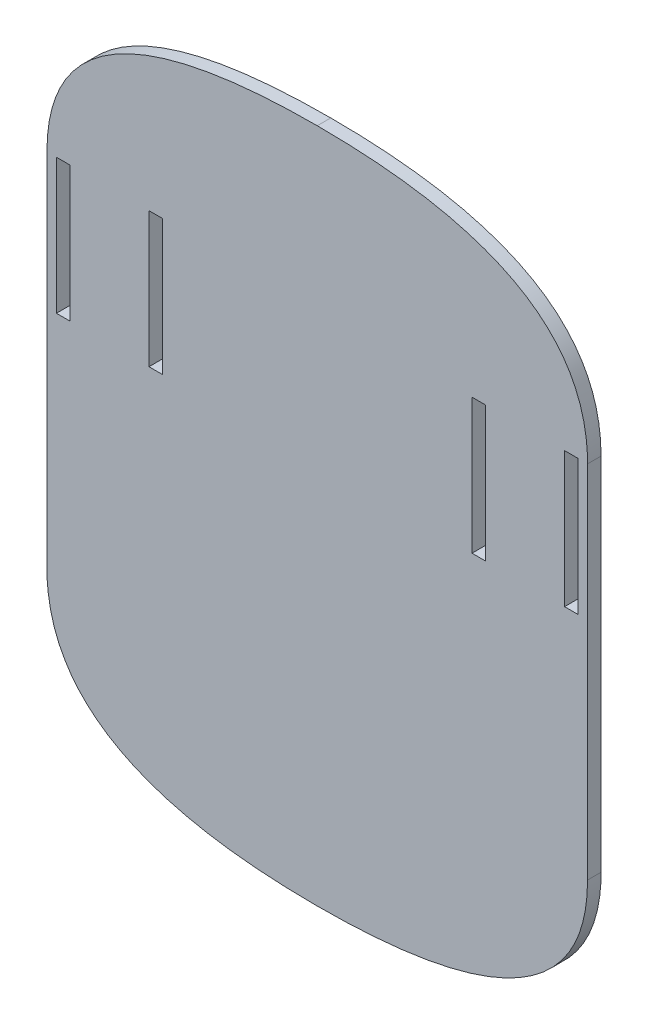
SolidWorks part; units mm, degrees
ref_plane "Front Plane" through (0, 0, 0) normal (0, 0, 1) x (1, 0, 0)
ref_plane "Top Plane" through (0, 0, 0) normal (0, 1, 0) x (1, 0, 0)
ref_plane "Right Plane" through (0, 0, 0) normal (1, 0, 0) x (0, 0, -1)
sketch "Sketch1" plane through (0, 0, 0) normal (0, 0, 1) x (1, 0, 0)
  line L1 (0, 0) -> (203.2, 0)
  line L2 (0, 0) -> (0, 254)
  line L3 (0, 254) -> (203.2, 254)
  line L4 (203.2, 0) -> (203.2, 254)
  dimension "D1" = 254
  dimension "D2" = 203.2
extrude "Boss-Extrude1" add sketch "Sketch1" along normal blind 5.08
fillet "Fillet1" radius 59.2667 4 edges at (203.2, 254, 2.54) (0, 254, 2.54) (203.2, 0, 2.54) (0, 0, 2.54)
sketch "Sketch2" plane through (0, 0, 5.08) normal (0, 0, 1) x (1, 0, 0)
  line L0 (0, 194.7333) -> (203.2, 194.7333) construction
sketch "Sketch3" plane through (0, 0, 5.08) normal (0, 0, 1) x (1, 0, 0)
  line L0 (0, 143.9333) -> (203.2, 143.9333) construction
  line L1 (0, 194.7333) -> (0, 59.2667) construction
  line L2 (203.2, 59.2667) -> (203.2, 194.7333) construction
sketch "Sketch4" plane through (0, 0, 5.08) normal (0, 0, 1) x (1, 0, 0)
  line L1 (-233.8282, 83.4373) -> (-176.6782, 83.4373) construction
  line L2 (-233.8282, 83.4373) -> (-233.8282, 26.2873) construction
  line L3 (-233.8282, 26.2873) -> (-176.6782, 26.2873) construction
  line L4 (-176.6782, 83.4373) -> (-176.6782, 26.2873) construction
  dimension "D1" = 57.15
  dimension "D2" = 57.15
sketch "Sketch5" plane through (0, 0, 5.08) normal (0, 0, 1) x (1, 0, 0)
  line L1 (-223.862, 148.2955) -> (-135.0034, 148.2955) construction
  line L2 (-223.862, 148.2955) -> (-223.862, 207.1496) construction
  line L3 (-223.862, 207.1496) -> (-135.0034, 207.1496) construction
  line L4 (-135.0034, 148.2955) -> (-135.0034, 207.1496) construction
  dimension "D1" = 88.8585
sketch "Sketch6" plane through (0, 0, 5.08) normal (0, 0, 1) x (1, 0, 0)
  line L1 (-299.8233, 201.2984) -> (-270.6133, 201.2984) construction
  line L2 (-299.8233, 201.2984) -> (-299.8233, 103.2544) construction
  line L3 (-299.8233, 103.2544) -> (-270.6133, 103.2544) construction
  line L4 (-270.6133, 201.2984) -> (-270.6133, 103.2544) construction
  dimension "D1" = 29.21
  dimension "D2" = 98.044
sketch "Sketch7" plane through (0, 0, 5.08) normal (0, 0, 1) x (1, 0, 0)
  line L0 (203.2, 59.2667) -> (203.2, 194.7333) construction
  line L1 (3.556, 194.7333) -> (8.636, 194.7333)
  line L2 (3.556, 194.7333) -> (3.556, 143.9333)
  line L3 (3.556, 143.9333) -> (8.636, 143.9333)
  line L4 (8.636, 194.7333) -> (8.636, 143.9333)
  line L5 (38.354, 194.7333) -> (43.434, 194.7333)
  line L6 (0, 194.7333) -> (203.2, 194.7333) construction
  line L7 (0, 143.9333) -> (203.2, 143.9333) construction
  line L8 (0, 194.7333) -> (0, 59.2667) construction
  line L9 (194.564, 194.7333) -> (199.644, 194.7333)
  line L10 (194.564, 194.7333) -> (194.564, 143.9333)
  line L11 (194.564, 143.9333) -> (199.644, 143.9333)
  line L12 (199.644, 194.7333) -> (199.644, 143.9333)
  line L13 (38.354, 194.7333) -> (38.354, 143.9333)
  line L14 (38.354, 143.9333) -> (43.434, 143.9333)
  line L15 (43.434, 194.7333) -> (43.434, 143.9333)
  line L16 (159.766, 194.7333) -> (164.846, 194.7333)
  line L17 (159.766, 194.7333) -> (159.766, 143.9333)
  line L18 (159.766, 143.9333) -> (164.846, 143.9333)
  line L19 (164.846, 194.7333) -> (164.846, 143.9333)
  point P4 (0, 0)
  point P5 (0, 0)
  point P6 (0, 0)
  point P7 (0, 0)
  point P8 (24.2631, 106.9382)
  point P9 (0, 0)
  point P10 (0, 0)
  point P11 (19.2548, 169.2746)
  point P12 (24.1768, 183.0926)
  point P13 (24.9948, 169.9741)
  point P14 (11.4866, 169.0266)
  point P15 (43.0252, 119.2404)
  point P16 (0, 0)
  point P17 (0, 0)
  dimension "D2" = 3.556
  dimension "D3" = 3.556
  dimension "D4" = 5.08
  dimension "D5" = 5.08
  dimension "D6" = 5.08
  dimension "D7" = 29.718
  dimension "D8" = 29.718
extrude "Cut-Extrude1" cut sketch "Sketch7" against normal through all
equation "\"FoamCore\" = \".2\""
equation "\"MDF\" = \".2\""
equation "\"GMaterial\"= \".2\""
equation "\"PVCMountDiameter\" = \"0.5in\""
equation "\"PVCMountDistanceToEdge\" = \"0.5\""
equation "\"PVCThickness\" = \"0.2in\""
equation "\"BaseWidth\" = \"8in\""
equation "\"BaseLength\" = \"10in\""
equation "\"BallDiameter\" = \"1.57in\""
equation "\"BaseGap\" = \"4in\""
equation "\"FunnelTopDiameter\" = \"8in\""
equation "\"FunnelTopDepth\" = \"1.5in\""
equation "\"BallGap\" = \"0.1in\""
equation "\"FunnelLength\" = 6in"
equation "\"FunnelMaterial\" = 0.1in"
equation "\"FunnelLowerDiameter\" = \"BallDiameter\"+\"BallGap\"+\"FunnelMaterial\"*2"
equation "\"FunnelDepth\" = 1.5in"
equation "\"AmmoFeederLength\" = 8in "
equation "\"AmmoFeederCutoffLength\" = 6in"
equation "\"WheelThickness\" = 0.5in"
equation "\"LauncherWheelDiameter\" = 60mm"
equation "\"MotorFrontLength\" = 0.95in"
equation "\"MotorBodyTotalLength\" = 2.03in"
equation "\"MotorFrontDiameter\" = 1.5in"
equation "\"MotorLowerDriveshaftDiameter\" = 0.46in"
equation "\"MotorLowerDriveshaftThickness\" = 0.25in"
equation "\"MotorFullDriveshaftLength\" = 0.78in"
equation "\"MotorDriveshaftDiameter\" = 0.23in"
equation "\"MotorDriveshaftFlatThickness\" = 0.2in"
equation "\"MotorRearDiameter\" = 31.9mm"
equation "\"MotorDriveshaftBottomToTop\" = 31.1mm"
equation "\"MotorFlatDriveshaftLength\" = 11.7mm"
equation "\"MotorDistanceBetweenLowerandTopHoles\" = 0.5in"
equation "\"MotorMountsDistanceFromEdge\" = 0.06in"
equation "\"MotorScrewMountDiameter\" = 0.1in"
equation "\"MotorScrewMountDepth\" = 0.13in"
equation "\"HBRidgeScrewHoleDeep\" = 0.18in"
equation "\"D1@Sketch1\"=\"BaseLength\""
equation "\"D2@Sketch1\"=\"BaseWidth\""
equation "\"D1@Boss-Extrude1\"=\"MDF\""
equation "\"D1@Fillet1\"=(\"BaseLength\"/3)-(\"MotorMountWidth\"/2)"
equation "\"FunnelBendLength\" = 2*pi*\"FunnelLowerDiameter\"/2*135"
equation "\"MotorMountWidth\" = \"2in\""
equation "\"D1@Sketch3\"=\"MotorMountWidth\""
equation "\"HBridgeWidth\" = 2.25in"
equation "\"HBridgeLength\" = 1.40in"
equation "\"D1@Sketch4\"=\"HBridgeWidth\""
equation "\"D2@Sketch4\"=\"HBridgeWidth\""
equation "\"UnoWidth\" = 3.13in"
equation "\"UnoLength\" = 3.06in"
equation "\"BatteryWidth\" = 1.15in"
equation "\"D1@Sketch6\"=\"BatteryWidth\""
equation "\"BatteryLength\" = 3.86in"
equation "\"D2@Sketch6\"=\"BatteryLength\""
equation "\"MotorMountLength\" = \"3.4in\""
equation "\"D1@Sketch7\"=\"FoamCore\""
equation "\"MotorMountToEdgeGap\" = \"0.14in\""
equation "\"D2@Sketch7\"=\"MotorMountToEdgeGap\""
equation "\"D3@Sketch7\"=\"MotorMountToEdgeGap\""
equation "\"D4@Sketch7\"=\"MDF\""
equation "\"D5@Sketch7\"=\"MDF\""
equation "\"D6@Sketch7\"=\"MDF\""
equation "\"MotorMountToMountGap\" = \"1.17in\""
equation "\"D7@Sketch7\"=\"MotorMountToMountGap\""
equation "\"D8@Sketch7\"=\"MotorMountToMountGap\""
equation "\"D2@Fillet1\"=\"BaseWidth\"/2"
equation "\"BatteryHeight\" = 3.86in"
equation "\"MotorToEdgeGap\" = \"0.14in\""
